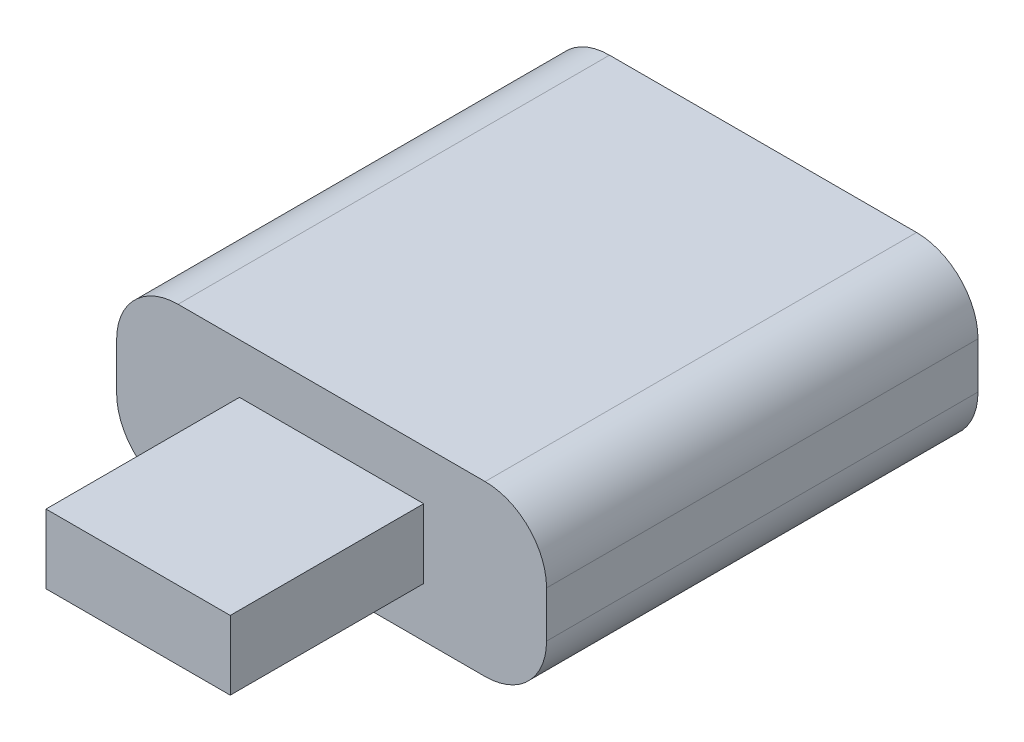
SolidWorks part; units mm, degrees
ref_plane "Front Plane" through (0, 0, 0) normal (0, 0, 1) x (1, 0, 0)
ref_plane "Top Plane" through (0, 0, 0) normal (0, 1, 0) x (1, 0, 0)
ref_plane "Right Plane" through (0, 0, 0) normal (1, 0, 0) x (0, 0, -1)
sketch "Sketch1" plane through (0, 0, 0) normal (0, 1, 0) x (1, 0, 0)
  line L1 (-14, 14.05) -> (14, 14.05)
  line L2 (-14, 14.05) -> (-14, -14.05)
  line L3 (-14, -14.05) -> (14, -14.05)
  line L4 (14, 14.05) -> (14, -14.05)
  line L5 (-14, 14.05) -> (14, -14.05) construction
  line L6 (-14, -14.05) -> (14, 14.05) construction
  line L7 (-6, -14.05) -> (6, -14.05)
  line L8 (-6, -14.05) -> (-6, -26.65)
  line L9 (-6, -26.65) -> (6, -26.65)
  line L10 (6, -14.05) -> (6, -26.65)
  point P0 (0, 0)
  point P10 (0, 0)
  point P11 (0, -26.65)
  dimension "D1" = 12
  dimension "D2" = 12.6
  dimension "D3" = 28.1
  dimension "D4" = 28
extrude "Boss-Extrude1" add sketch "Sketch1" along normal blind 5.5 and the other way blind 5.5 contours L4 L1 L2 L3 region at (0, 0, 0)
extrude "Boss-Extrude2" add sketch "Sketch1<4>" along normal blind 2.25 and the other way blind 2.25 contours L10 L3 L8 L9 region at (0, 0, 20.35)
sketch "Sketch1<4>" plane through (0, 0, 0) normal (0, 1, 0) x (1, 0, 0) same geometry as "Sketch1"
fillet "Fillet2" radius 4 4 edges at (-14, -5.5, 0) (-14, 5.5, 0) (14, -5.5, 0) (14, 5.5, 0)
